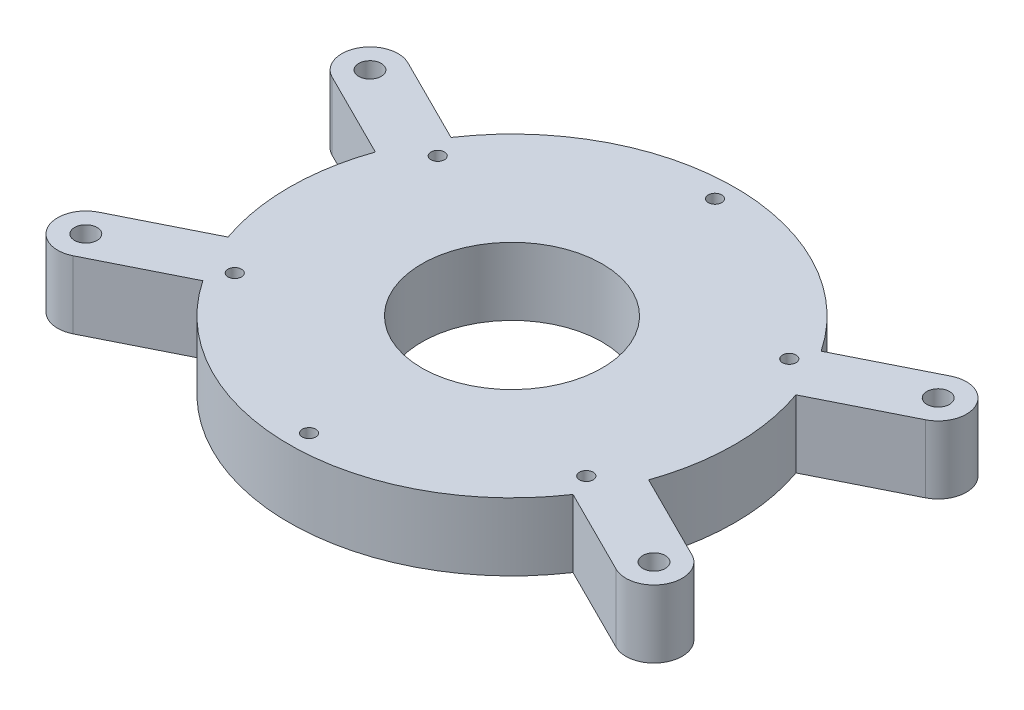
SolidWorks part; units mm, degrees
ref_plane "前视基准面" through (0, 0, 0) normal (0, 0, 1) x (1, 0, 0)
ref_plane "上视基准面" through (0, 0, 0) normal (0, 1, 0) x (1, 0, 0)
ref_plane "右视基准面" through (0, 0, 0) normal (1, 0, 0) x (0, 0, -1)
sketch "草图1" plane through (0, 0, 0) normal (0, 1, 0) x (1, 0, 0)
  line L0 (65.782, 25.9101) -> (46.6233, 16.3287)
  line L1 (60.1908, 37.0899) -> (41.0322, 27.5085)
  line L2 (0, 135.0816) -> (0, -134.5462) construction
  line L3 (161.8892, 80.9621) -> (-87.1466, -43.5827) construction
  line L7 (-65.782, 25.9101) -> (-46.6233, 16.3287)
  line L8 (-50, 21.5) -> (50, 21.5) construction
  line L9 (-50, 21.5) -> (-50, -21.5) construction
  line L10 (-50, -21.5) -> (50, -21.5) construction
  line L11 (50, 21.5) -> (50, -21.5) construction
  line L12 (-60.1908, 37.0899) -> (-41.0322, 27.5085)
  line L13 (-133.256, 0) -> (145.6129, 0) construction
  line L14 (65.782, -25.9101) -> (46.6233, -16.3287)
  line L15 (60.1908, -37.0899) -> (41.0322, -27.5085)
  line L16 (-65.782, -25.9101) -> (-46.6233, -16.3287)
  line L17 (-60.1908, -37.0899) -> (-41.0322, -27.5085)
  circle A0 centre (0, 0) radius 20
  circle A1 centre (0, 0) radius 49.4
  circle A2 centre (62.9864, 31.5) radius 6.25
  circle A6 centre (-62.9864, 31.5) radius 6.25
  circle A7 centre (62.9864, -31.5) radius 6.25
  circle A8 centre (-62.9864, -31.5) radius 6.25
  point P19 (0, 21.5)
  point P20 (50, 0)
  point P41 (0, 0)
  dimension "D2" = 12.5
  dimension "D5" = 98.8
  dimension "D7" = 40
  dimension "D1" = 63.43
  dimension "D3" = 100
  dimension "D4" = 43
  dimension "D6" = 10
extrude "凸台-拉伸1" add sketch "草图1" along normal blind 15 contours A1 A0 | L12 A6 L7 A1 | A8 L17 A1 L16 | A8 | L15 A7 L14 A1 | A7 | A2 | A2 L1 A1 L0 | A6 region at (51.3835, 0, -25.6973) region at (62.9864, 0, -31.5) region at (47.3234, 0, -8.0473) region at (51.3835, 0, 25.6973) region at (-51.3835, 0, -25.6973) region at (62.9864, 0, 31.5) region at (-51.3835, 0, 25.6973) region at (-62.9864, 0, 31.5)
sketch "草图2" plane through (0, 15, 0) normal (0, 1, 0) x (1, 0, 0)
  line L0 (0, 78.1952) -> (0, -57.2274) construction
  line L1 (-93.9988, 0) -> (82.0699, 0) construction
  circle A0 centre (-62.9864, 31.5) radius 2.5
  arc A1 (-60.1908, 37.0899) -> (-65.782, 25.9101) centre (-62.9864, 31.5) ccw construction
  dimension "D1" = 5
extrude "切除-拉伸1" cut sketch "草图2" against normal blind 10
cosmetic thread "装饰螺纹线6" parameters "D1"=5, "D2"=6
mirror "镜向1" about plane through (0, 0, 0) normal (0, 0, 1) of "切除-拉伸1"
cosmetic thread "装饰螺纹线7" parameters "D1"=5, "D2"=6
mirror "镜向2" about plane through (0, 0, 0) normal (1, 0, 0) of "镜向1"
cosmetic thread "装饰螺纹线8" parameters "D1"=5, "D2"=6
cosmetic thread "装饰螺纹线9" parameters "D1"=5, "D2"=6
ref_plane "基准面1" through (0, 7.5, 0) normal (0, -1, 0) x (-1, 0, 0)
sketch "草图3" plane through (0, 0, 0) normal (0, -1, 0) x (1, 0, 0)
  line L1 (-65.782, 25.9101) -> (-46.6233, 16.3287) construction
  circle A0 centre (-54.0425, 27.0271) radius 2.5
  circle A2 centre (-62.9864, 31.5) radius 2.0501 construction
  arc A3 (-60.1908, 37.0899) -> (-65.782, 25.9101) centre (-62.9864, 31.5) ccw construction
  dimension "D1" = 5
  dimension "D3" = 10
  dimension "D2" = 6.25
extrude "切除-拉伸2" cut sketch "草图3" against normal blind 10
cosmetic thread "装饰螺纹线5" parameters "D2"=6
mirror "镜向3" about plane through (0, 0, 0) normal (1, 0, 0) of "切除-拉伸2"
cosmetic thread "装饰螺纹线10" parameters "D2"=6
mirror "镜向4" about plane through (0, 0, 0) normal (0, 0, 1) of "镜向3"
cosmetic thread "装饰螺纹线11" parameters "D2"=6
cosmetic thread "装饰螺纹线12" parameters "D2"=6
sketch "草图4" plane through (0, 0, 0) normal (0, -1, 0) x (1, 0, 0)
  circle A0 centre (0, -45) radius 1.5
  dimension "D1" = 3
  dimension "D2" = 45
extrude "切除-拉伸3" cut sketch "草图4" against normal through all
cosmetic thread "装饰螺纹线13" parameters "D2"=4
pattern_circular "阵列(圆周)1" count 6 over 360 about axis through (0, 0, 0) along (0, 1, 0) of "切除-拉伸3"
cosmetic thread "装饰螺纹线14" parameters "D2"=4
cosmetic thread "装饰螺纹线15" parameters "D2"=4
cosmetic thread "装饰螺纹线16" parameters "D2"=4
cosmetic thread "装饰螺纹线17" parameters "D2"=4
cosmetic thread "装饰螺纹线18" parameters "D2"=4
